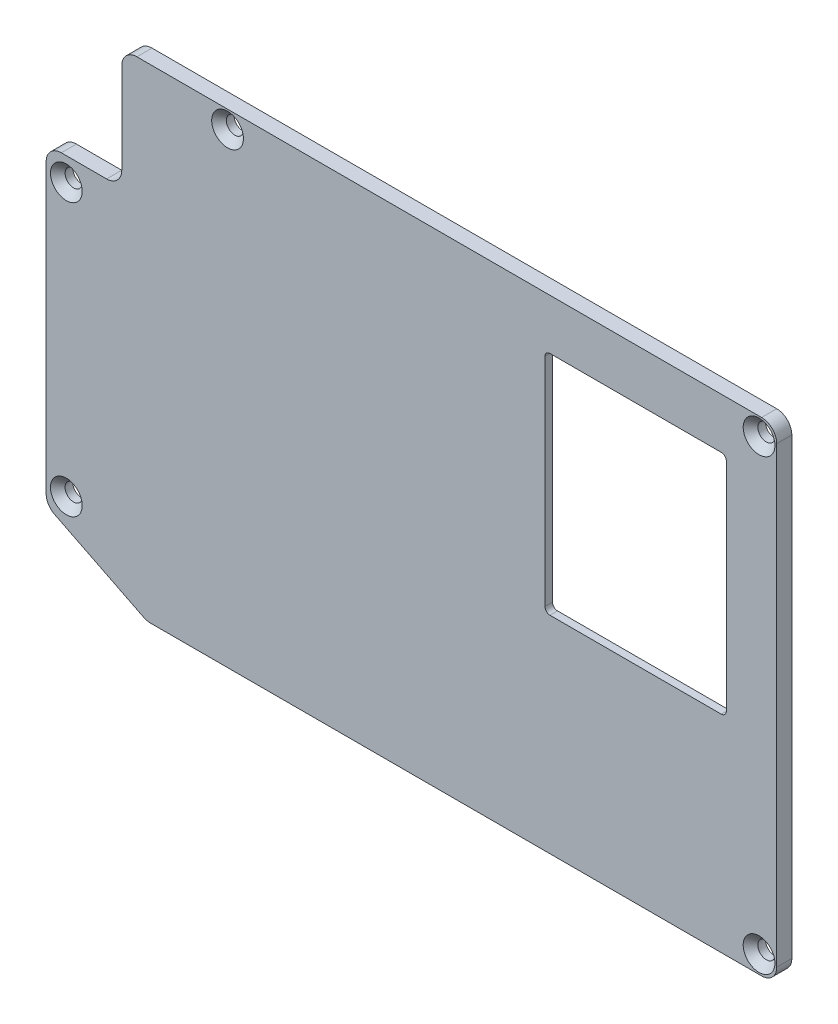
SolidWorks part; units mm, degrees
material "6061 合金"
ref_plane "前视基准面" through (0, 0, 0) normal (0, 0, 1) x (1, 0, 0)
ref_plane "上视基准面" through (0, 0, 0) normal (0, 1, 0) x (1, 0, 0)
ref_plane "右视基准面" through (0, 0, 0) normal (1, 0, 0) x (0, 0, -1)
sketch "草图1" plane through (0, 0, 0) normal (0, 0, 1) x (1, 0, 0)
  line L0 (15, 96) -> (15, 72)
  line L1 (20, 0) -> (145, 0)
  line L2 (0, 10) -> (0, 72)
  line L3 (15, 96) -> (145, 96)
  line L4 (145, 0) -> (145, 96)
  line L5 (0, 10) -> (20, 0)
  line L6 (15, 72) -> (0, 72)
  dimension "D1" = 125
  dimension "D2" = 96
  dimension "D3" = 130
  dimension "D4" = 10
  dimension "D5" = 24
  dimension "D6" = 145
extrude "凸台-拉伸1" add sketch "草图1" along normal blind 3
hole_wizard "M3 平头机械螺钉的锥形沉头孔1" positions "草图3" profile "草图2" countersink size "M3" standard "Ansi Metric" end condition through all
sketch "草图3" plane through (0, 0, 3) normal (0, 0, 1) x (1, 0, 0)
  point P0 (141.5, 92.5)
  point P9 (141.5, 3.5)
  point P18 (4, 67.4271)
  point P21 (4, 13.4271)
  point P24 (36, 92.5)
sketch "草图2" plane through (141.5, 92.5, 3) normal (1, 0, 0) x (0, -1, 0)
  line L0 (0, 0) -> (0, 3)
  line L1 (0, 3) -> (1.7, 3)
  line L2 (1.7, 3) -> (1.7, 1.45)
  line L3 (1.7, 1.45) -> (3.15, 0)
  line L5 (3.15, 0) -> (0, 0)
  line L6 (-1.7, 1.45) -> (-3.15, 0) construction
  line L11 (0, -6.35) -> (0, 107.95) construction
  dimension "通孔孔直径" = 3.4
  dimension "通孔孔深度" = 3
  dimension "近端锥形沉头孔直径" = 6.3
  dimension "近端锥形沉头孔角度" = 90
fillet "圆角1" radius 3 2 edges at (145, 96, 1.5) (145, 0, 1.5)
fillet "圆角2" radius 3 4 edges at (20, 0, 1.5) (15, 96, 1.5) (0, 72, 1.5) (0, 10, 1.5)
ref_plane "基准面1" through (0, 48, 0) normal (0, -1, 0) x (-1, 0, 0)
sketch "草图4" plane through (0, 0, 0) normal (0, 0, -1) x (-1, 0, 0)
  line L0 (-133.5858, 92) -> (-141, 84.5858)
  line L1 (-141, 84.5858) -> (-141, 12.1213)
  line L2 (-141, 12.1213) -> (-132.8787, 4)
  line L3 (-132.8787, 4) -> (-22.0623, 4)
  line L4 (-22.0623, 4) -> (-13, 8.5312)
  line L5 (-13, 8.5312) -> (-13, 24)
  line L6 (-13, 24) -> (-4, 27)
  line L7 (-4, 27) -> (-4, 50.4741)
  line L8 (-4, 50.4741) -> (-19.5, 68.9463)
  line L9 (-19.5, 68.9463) -> (-19.5, 91)
  line L10 (-45.8284, 92) -> (-39.8284, 86)
  line L11 (-45.8284, 92) -> (-133.5858, 92)
  line L12 (-132.7574, 93) -> (-121, 93) construction
  line L13 (-140.5355, 86.4645) -> (-134.8787, 92.1213) construction
  line L14 (-142, 13.0711) -> (-142, 82.9289) construction
  line L15 (-121, 3) -> (-132.7574, 3) construction
  line L16 (-134.8787, 3.8787) -> (-140.5355, 9.5355) construction
  line L17 (-14.7639, 5.9721) -> (-19.6525, 3.5279) construction
  line L18 (-12, 22) -> (-12, 10.4443) construction
  line L20 (-3, 56) -> (-3, 26) construction
  line L23 (-39.8284, 86) -> (-32.1716, 86)
  line L25 (-32.1716, 86) -> (-27.1716, 91)
  line L26 (-27.1716, 91) -> (-19.5, 91)
  line L27 (-43.1213, 92.1213) -> (-39.8787, 88.8787) construction
  line L28 (-37.7574, 88) -> (-34.2426, 88) construction
  line L29 (-32.1213, 88.8787) -> (-28.5858, 92.4142) construction
  line L30 (-27.1716, 93) -> (-20, 93) construction
  line L31 (-18, 91) -> (-18, 70) construction
  line L32 (-11.4008, 68.6284) -> (-3.0019, 58.6189) construction
  line L33 (-6, 23) -> (-11, 23) construction
  dimension "D1" = 1
  dimension "D2" = 1
  dimension "D3" = 1
  dimension "D4" = 1
  dimension "D5" = 1.5
  dimension "D6" = 1.5
  dimension "D7" = 1
  dimension "D8" = 2
  dimension "D9" = 1
  dimension "D10" = 2
  dimension "D11" = 2
  dimension "D12" = 2
  dimension "D13" = 1.5
  dimension "D14" = 6
  dimension "D15" = 1
  dimension "D16" = 3
extrude "切除-拉伸1" cut sketch "草图4" against normal offset from surface (1.2 mm away) 1.8 up to face at (144.65, 92.5, 3)
sketch "草图5" plane through (0, 0, 1.2) normal (0, 0, -1) x (-1, 0, 0)
  line L0 (-45.8284, 92) -> (-133.5858, 92) construction
  line L1 (-93, 92) -> (-78, 92)
  line L2 (-93, 92) -> (-93, 4)
  line L3 (-93, 4) -> (-78, 4)
  line L4 (-78, 92) -> (-78, 4)
  line L5 (-132.8787, 4) -> (-22.0623, 4) construction
  line L6 (-145, 3) -> (-145, 93) construction
  dimension "D1" = 15
  dimension "D2" = 52
extrude "切除-拉伸2" cut sketch "草图5" against normal offset from surface (0.8 mm away) 1 up to face at (144.65, 92.5, 3)
fillet "圆角5" radius 3 11 edges at (13, 8.5312, 0.6) (22.0623, 4, 0.6) (132.8787, 4, 0.6) (141, 12.1213, 0.6) (141, 84.5858, 0.6) (133.5858, 92, 0.6) (4, 50.4741, 0.6) (4, 27, 0.6) (45.8284, 92, 0.6) (27.1716, 91, 0.6) (19.5, 91, 0.6)
fillet "圆角6" radius 5 4 edges at (13, 24, 0.6) (19.5, 68.9463, 0.6) (32.1716, 86, 0.6) (39.8284, 86, 0.6)
fillet "圆角7" radius 3 4 edges
sketch "草图6" plane through (0, 0, 0) normal (0, 0, -1) x (-1, 0, 0)
  line L0 (-141, 83.3431) -> (-141, 13.364) construction
  line L1 (-141, 56) -> (-142, 56)
  line L2 (-141, 56) -> (-141, 40)
  line L3 (-141, 40) -> (-142, 40)
  line L4 (-142, 56) -> (-142, 40)
  line L5 (-142, 13.0711) -> (-142, 82.9289) construction
  line L6 (-145, 48) -> (-124.4765, 48) construction
  line L7 (-145, 3) -> (-145, 93) construction
  line L8 (-4, 29.1623) -> (-4, 49.3822) construction
  line L9 (-4, 46) -> (-3, 46)
  line L10 (-4, 46) -> (-4, 34)
  line L11 (-4, 34) -> (-3, 34)
  line L12 (-3, 46) -> (-3, 34)
  line L13 (-3, 56) -> (-3, 26) construction
  line L14 (-20.7082, 0) -> (-142, 0) construction
  line L15 (-131.636, 4) -> (-22.7705, 4) construction
  line L16 (-82, 4) -> (-70, 4)
  line L17 (-82, 4) -> (-82, 3)
  line L18 (-82, 3) -> (-70, 3)
  line L19 (-70, 4) -> (-70, 3)
  line L20 (-21.8885, 3) -> (-99, 3) construction
  line L21 (0, 69) -> (0, 11.8541) construction
  line L22 (-47.0711, 92) -> (-132.3431, 92) construction
  line L23 (-82, 92) -> (-70, 92)
  line L24 (-82, 92) -> (-82, 93)
  line L25 (-82, 93) -> (-70, 93)
  line L26 (-70, 92) -> (-70, 93)
  line L27 (-99, 93) -> (-45.2426, 93) construction
  dimension "D1" = 16
  dimension "D2" = 12
  dimension "D3" = 34
  dimension "D4" = 12
  dimension "D5" = 70
  dimension "D6" = 12
  dimension "D7" = 70
extrude "凸台-拉伸2" add sketch "草图6" along normal blind 1
fillet "圆角8" radius 3 1 edges at (15, 72, 1.5)
chamfer "倒角1" distance 1 angle 45 8 edges at (3.5, 46, -1) (3.5, 34, -1) (70, 3.5, -1) (82, 3.5, -1) (141.5, 56, -1) (141.5, 40, -1) (82, 92.5, -1) (70, 92.5, -1)
sketch "草图9" plane through (0, 0, 1.2) normal (0, 0, -1) x (-1, 0, 0)
  line L0 (-95, 92) -> (-95, 34)
  line L1 (-95, 34) -> (-141, 34)
  line L6 (-140.1213, 11.2426) -> (-133.7574, 4.8787)
  line L7 (-131.636, 4) -> (-90, 4)
  line L8 (-93, 7) -> (-93, 89)
  line L9 (-90, 92) -> (-132.3431, 92)
  line L10 (-134.4645, 91.1213) -> (-140.1213, 85.4645)
  line L11 (-141, 83.3431) -> (-141, 13.364)
  line L15 (-95, 92) -> (-132.3431, 92)
  line L16 (-134.4645, 91.1213) -> (-140.1213, 85.4645)
  line L17 (-141, 83.3431) -> (-141, 34)
  arc A6 (-133.7574, 4.8787) -> (-131.636, 4) centre (-131.636, 7) ccw
  arc A7 (-93, 7) -> (-90, 4) centre (-90, 7) ccw
  arc A8 (-90, 92) -> (-93, 89) centre (-90, 89) ccw
  arc A9 (-132.3431, 92) -> (-134.4645, 91.1213) centre (-132.3431, 89) ccw
  arc A10 (-140.1213, 85.4645) -> (-141, 83.3431) centre (-138, 83.3431) ccw
  arc A11 (-141, 13.364) -> (-140.1213, 11.2426) centre (-138, 13.364) ccw
  arc A15 (-132.3431, 92) -> (-134.4645, 91.1213) centre (-132.3431, 89) ccw
  arc A16 (-140.1213, 85.4645) -> (-141, 83.3431) centre (-138, 83.3431) ccw
  dimension "D2" = 58
  dimension "D3" = 46
  dimension "D1" = 0
extrude "凸台-拉伸4" add sketch "草图9" along normal blind 1.2
sketch "草图7" plane through (0, 0, 3) normal (0, 0, 1) x (1, 0, 0)
  line L0 (145, 3) -> (145, 93) construction
  line L1 (100, 86) -> (134, 86)
  line L2 (99, 85) -> (99, 42)
  line L3 (100, 41) -> (134, 41)
  line L4 (135, 85) -> (135, 42)
  line L5 (142, 96) -> (18, 96) construction
  arc A0 (99, 42) -> (100, 41) centre (100, 42) ccw
  arc A1 (134, 41) -> (135, 42) centre (134, 42) ccw
  arc A2 (135, 85) -> (134, 86) centre (134, 85) ccw
  arc A3 (99, 85) -> (100, 86) centre (100, 85) cw
  point P10 (99, 41)
  point P15 (135, 86)
  point P18 (99, 86)
  dimension "D5" = 1
  dimension "D1" = 36
  dimension "D2" = 45
  dimension "D3" = 10
  dimension "D4" = 10
extrude "切除-拉伸3" cut sketch "草图7" against normal blind 10
sketch "草图10" plane through (0, 0, 0) normal (0, 0, -1) x (-1, 0, 0)
  line L1 (-135, 89) -> (-99, 89)
  line L2 (-138, 86) -> (-138, 41)
  line L3 (-135, 38) -> (-99, 38)
  line L4 (-96, 86) -> (-96, 41)
  line L5 (-100, 86) -> (-134, 86) construction
  line L6 (-99, 42) -> (-99, 85) construction
  line L7 (-134, 41) -> (-100, 41) construction
  line L8 (-135, 85) -> (-135, 42) construction
  arc A0 (-138, 41) -> (-135, 38) centre (-135, 41) ccw
  arc A1 (-96, 41) -> (-99, 38) centre (-99, 41) cw
  arc A2 (-96, 86) -> (-99, 89) centre (-99, 86) ccw
  arc A3 (-138, 86) -> (-135, 89) centre (-135, 86) cw
  dimension "D5" = 3
  dimension "D1" = 3
  dimension "D2" = 3
  dimension "D3" = 3
  dimension "D4" = 3
extrude "切除-拉伸5" cut sketch "草图10" against normal offset from surface (1.5 mm away) 1.5 up to face at (117, 63.5, 3)
sketch "草图12" plane through (0, 0, 1.5) normal (0, 0, -1) x (-1, 0, 0)
  line L0 (-135, 39.5) -> (-99, 39.5)
  line L1 (-97.5, 41) -> (-97.5, 86)
  line L2 (-99, 87.5) -> (-135, 87.5)
  line L3 (-136.5, 86) -> (-136.5, 41)
  line L4 (-135, 38) -> (-99, 38)
  line L5 (-96, 41) -> (-96, 86)
  line L6 (-99, 89) -> (-135, 89)
  line L7 (-138, 86) -> (-138, 41)
  line L8 (-135, 38) -> (-99, 38)
  line L9 (-96, 41) -> (-96, 86)
  line L10 (-99, 89) -> (-135, 89)
  line L11 (-138, 86) -> (-138, 41)
  arc A0 (-99, 39.5) -> (-97.5, 41) centre (-99, 41) ccw
  arc A1 (-97.5, 86) -> (-99, 87.5) centre (-99, 86) ccw
  arc A2 (-135, 87.5) -> (-136.5, 86) centre (-135, 86) ccw
  arc A3 (-136.5, 41) -> (-135, 39.5) centre (-135, 41) ccw
  arc A4 (-138, 41) -> (-135, 38) centre (-135, 41) ccw
  arc A5 (-99, 38) -> (-96, 41) centre (-99, 41) ccw
  arc A6 (-96, 86) -> (-99, 89) centre (-99, 86) ccw
  arc A7 (-135, 89) -> (-138, 86) centre (-135, 86) ccw
  arc A8 (-138, 41) -> (-135, 38) centre (-135, 41) ccw
  arc A9 (-99, 38) -> (-96, 41) centre (-99, 41) ccw
  arc A10 (-96, 86) -> (-99, 89) centre (-99, 86) ccw
  arc A11 (-135, 89) -> (-138, 86) centre (-135, 86) ccw
  dimension "D1" = 0
  dimension "D2" = 1.5
extrude "切除-拉伸6" cut sketch "草图12" against normal blind 0.4
fillet "圆角9" radius 2 2 edges at (141, 34, 0.6) (95, 92, 0.6)
fillet "圆角10" radius 4 1 edges at (95, 34, 0.6)
